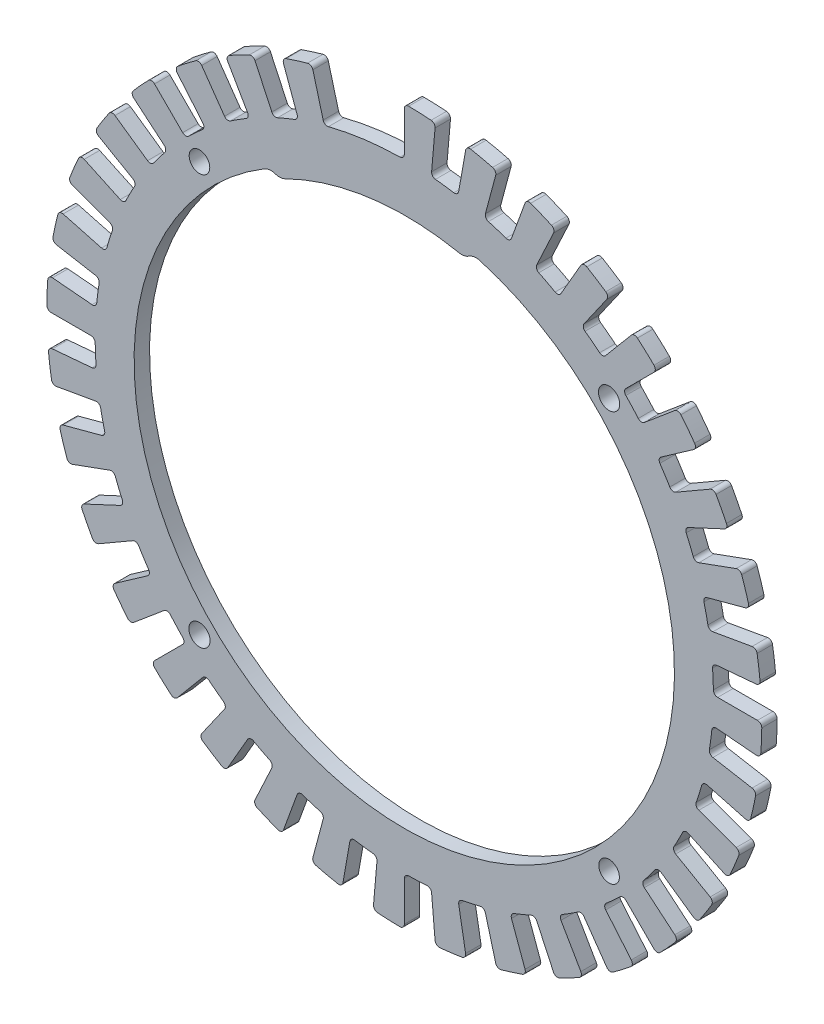
SolidWorks part; units mm, degrees
ref_plane "Front Plane" through (0, 0, 0) normal (0, 0, 1) x (1, 0, 0)
ref_plane "Top Plane" through (0, 0, 0) normal (0, 1, 0) x (1, 0, 0)
ref_plane "Right Plane" through (0, 0, 0) normal (1, 0, 0) x (0, 0, -1)
sketch "Sketch1" plane through (0, 0, 0) normal (0, 0, 1) x (1, 0, 0)
  line L0 (0, 82.7) -> (0, 71.5) construction
  line L1 (7.2078, 82.3853) -> (6.2316, 71.2279) construction
  line L2 (0, 71.5) -> (0, 0) construction
  line L3 (6.2316, 71.2279) -> (0, 0) construction
  line L4 (12.5883, 71.3918) -> (14.186, 80.4528) construction
  line L5 (12.5883, 71.3918) -> (0, 0) construction
  line L8 (0, 0) -> (47.3762, 47.3762) construction
  line L12 (50.5581, 50.5581) -> (47.3762, 47.3762) construction
  line L15 (47.3762, 47.3762) -> (44.1942, 44.1942) construction
  line L18 (7.3144, 72.1301) -> (6.3182, 72.2172) construction
  line L21 (7.3144, 72.1301) -> (7.2135, 71.1352) construction
  line L24 (12.5883, 71.3918) -> (11.6035, 71.5654) construction
  line L27 (11.6035, 71.5654) -> (11.4434, 70.5783) construction
  line L30 (1.0122, 82.6938) -> (1, 81.6939) construction
  line L33 (1, 81.6939) -> (0, 81.6939) construction
  line L36 (7.1201, 81.383) -> (6.1239, 81.4702) construction
  line L39 (6.1239, 81.4702) -> (6.1989, 82.4674) construction
  line L42 (7.1201, 81.383) -> (6.3182, 72.2172)
  line L45 (0, 81.6939) -> (0, 72.4931)
  line L48 (0, 72.4931) -> (-1, 72.4931) construction
  line L51 (-1, 72.4931) -> (-0.9862, 71.4932) construction
  line L109 (0, -82.7) -> (0, -71.5) [skipped]
  line L111 (14.3607, 81.4436) -> (12.4158, 70.4138) [skipped]
  line L115 (41.35, 71.6203) -> (35.75, 61.9208) [skipped]
  line L117 (53.1585, 63.3519) -> (45.9593, 54.7722) [skipped]
  line L118 (-63.3519, -53.1585) -> (-54.7722, -45.9593) [skipped]
  line L119 (63.3519, 53.1585) -> (54.7722, 45.9593) [skipped]
  line L121 (71.6203, 41.35) -> (61.9208, 35.75) [skipped]
  line L123 (77.7126, 28.2851) -> (67.188, 24.4544) [skipped]
  line L125 (81.4436, 14.3607) -> (70.4138, 12.4158) [skipped]
  line L127 (82.7, 0) -> (71.5, 0) [skipped]
  line L129 (81.4436, -14.3607) -> (70.4138, -12.4158) [skipped]
  line L131 (77.7126, -28.2851) -> (67.188, -24.4544) [skipped]
  line L133 (71.6203, -41.35) -> (61.9208, -35.75) [skipped]
  line L135 (63.3519, -53.1585) -> (54.7722, -45.9593) [skipped]
  line L137 (53.1585, -63.3519) -> (45.9593, -54.7722) [skipped]
  line L139 (41.35, -71.6203) -> (35.75, -61.9208) [skipped]
  line L141 (28.2851, -77.7126) -> (24.4544, -67.188) [skipped]
  line L142 (14.3607, -81.4436) -> (12.4158, -70.4138) [skipped]
  line L143 (34.9505, 74.9517) -> (30.2172, 64.801) [skipped]
  line L144 (47.4348, 67.7439) -> (41.0107, 58.5694) [skipped]
  line L145 (58.4777, 58.4777) -> (50.5581, 50.5581) [skipped]
  line L146 (67.7439, 47.4348) -> (58.5694, 41.0107) [skipped]
  line L147 (74.9517, 34.9505) -> (64.801, 30.2172) [skipped]
  line L148 (79.8821, 21.4043) -> (69.0637, 18.5056) [skipped]
  line L149 (82.3853, 7.2078) -> (71.2279, 6.2316) [skipped]
  line L150 (82.3853, -7.2078) -> (71.2279, -6.2316) [skipped]
  line L151 (79.8821, -21.4043) -> (69.0637, -18.5056) [skipped]
  line L152 (74.9517, -34.9505) -> (64.801, -30.2172) [skipped]
  line L153 (67.7439, -47.4348) -> (58.5694, -41.0107) [skipped]
  line L154 (58.4777, -58.4777) -> (50.5581, -50.5581) [skipped]
  line L155 (47.4348, -67.7439) -> (41.0107, -58.5694) [skipped]
  line L156 (34.9505, -74.9517) -> (30.2172, -64.801) [skipped]
  line L157 (21.4043, -79.8821) -> (18.5056, -69.0637) [skipped]
  line L158 (7.2078, -82.3853) -> (6.2316, -71.2279) [skipped]
  line L159 (-7.2078, -82.3853) -> (-6.2316, -71.2279) [skipped]
  line L160 (-21.4043, -79.8821) -> (-18.5056, -69.0637) [skipped]
  line L161 (-34.9505, -74.9517) -> (-30.2172, -64.801) [skipped]
  line L162 (-47.4348, -67.7439) -> (-41.0107, -58.5694) [skipped]
  line L163 (-58.4777, -58.4777) -> (-50.5581, -50.5581) [skipped]
  line L164 (-67.7439, -47.4348) -> (-58.5694, -41.0107) [skipped]
  line L165 (-74.9517, -34.9505) -> (-64.801, -30.2172) [skipped]
  line L166 (-79.8821, -21.4043) -> (-69.0637, -18.5056) [skipped]
  line L167 (-82.3853, -7.2078) -> (-71.2279, -6.2316) [skipped]
  line L168 (-82.3853, 7.2078) -> (-71.2279, 6.2316) [skipped]
  line L169 (-79.8821, 21.4043) -> (-69.0637, 18.5056) [skipped]
  line L170 (-74.9517, 34.9505) -> (-64.801, 30.2172) [skipped]
  line L171 (-67.7439, 47.4348) -> (-58.5694, 41.0107) [skipped]
  line L172 (-58.4777, 58.4777) -> (-50.5581, 50.5581) [skipped]
  line L173 (-47.4348, 67.7439) -> (-41.0107, 58.5694) [skipped]
  line L174 (-34.9505, 74.9517) -> (-30.2172, 64.801) [skipped]
  line L175 (-21.4043, 79.8821) -> (-18.5056, 69.0637) [skipped]
  line L176 (21.4043, 79.8821) -> (18.5056, 69.0637) [skipped]
  line L209 (0, 0) -> (-47.3762, -47.3762) construction
  line L210 (0, 0) -> (-47.3762, 47.3762) construction
  line L211 (0, 0) -> (47.3762, -47.3762) construction
  line L212 (14.186, 80.4528) -> (12.5883, 71.3918)
  line L213 (21.1439, 78.9102) -> (18.7626, 70.023)
  line L214 (27.941, 76.7671) -> (24.7941, 68.1212)
  line L215 (34.5253, 74.0398) -> (30.6369, 65.7011)
  line L216 (40.8469, 70.749) -> (36.2466, 62.7809)
  line L217 (46.8577, 66.9197) -> (41.5803, 59.3829)
  line L218 (52.5118, 62.5811) -> (46.5977, 55.5329)
  line L219 (57.7663, 57.7663) -> (51.2604, 51.2604)
  line L220 (62.5811, 52.5118) -> (55.5329, 46.5977)
  line L221 (66.9197, 46.8577) -> (59.3829, 41.5803)
  line L222 (70.749, 40.8469) -> (62.7809, 36.2466)
  line L223 (74.0398, 34.5253) -> (65.7011, 30.6369)
  line L224 (76.7671, 27.941) -> (68.1212, 24.7941)
  line L225 (78.9102, 21.1439) -> (70.023, 18.7626)
  line L226 (80.4528, 14.186) -> (71.3918, 12.5883)
  line L227 (81.383, 7.1201) -> (72.2172, 6.3182)
  line L228 (81.6939, 0) -> (72.4931, 0)
  line L229 (81.383, -7.1201) -> (72.2172, -6.3182)
  line L230 (80.4528, -14.186) -> (71.3918, -12.5883)
  line L231 (78.9102, -21.1439) -> (70.023, -18.7626)
  line L232 (76.7671, -27.941) -> (68.1212, -24.7941)
  line L233 (74.0398, -34.5253) -> (65.7011, -30.6369)
  line L234 (70.749, -40.8469) -> (62.7809, -36.2466)
  line L235 (66.9197, -46.8577) -> (59.3829, -41.5803)
  line L236 (62.5811, -52.5118) -> (55.5329, -46.5977)
  line L237 (57.7663, -57.7663) -> (51.2604, -51.2604)
  line L238 (52.5118, -62.5811) -> (46.5977, -55.5329)
  line L239 (46.8577, -66.9197) -> (41.5803, -59.3829)
  line L240 (40.8469, -70.749) -> (36.2466, -62.7809)
  line L241 (34.5253, -74.0398) -> (30.6369, -65.7011)
  line L242 (27.941, -76.7671) -> (24.7941, -68.1212)
  line L243 (21.1439, -78.9102) -> (18.7626, -70.023)
  line L244 (14.186, -80.4528) -> (12.5883, -71.3918)
  line L245 (7.1201, -81.383) -> (6.3182, -72.2172)
  line L246 (0, -81.6939) -> (0, -72.4931)
  line L247 (-7.1201, -81.383) -> (-6.3182, -72.2172)
  line L248 (-14.186, -80.4528) -> (-12.5883, -71.3918)
  line L249 (-21.1439, -78.9102) -> (-18.7626, -70.023)
  line L250 (-27.941, -76.7671) -> (-24.7941, -68.1212)
  line L251 (-34.5253, -74.0398) -> (-30.6369, -65.7011)
  line L252 (-40.8469, -70.749) -> (-36.2466, -62.7809)
  line L253 (-46.8577, -66.9197) -> (-41.5803, -59.3829)
  line L254 (-52.5118, -62.5811) -> (-46.5977, -55.5329)
  line L255 (-57.7663, -57.7663) -> (-51.2604, -51.2604)
  line L256 (-62.5811, -52.5118) -> (-55.5329, -46.5977)
  line L257 (-66.9197, -46.8577) -> (-59.3829, -41.5803)
  line L258 (-70.749, -40.8469) -> (-62.7809, -36.2466)
  line L259 (-74.0398, -34.5253) -> (-65.7011, -30.6369)
  line L260 (-76.7671, -27.941) -> (-68.1212, -24.7941)
  line L261 (-78.9102, -21.1439) -> (-70.023, -18.7626)
  line L262 (-80.4528, -14.186) -> (-71.3918, -12.5883)
  line L263 (-81.383, -7.1201) -> (-72.2172, -6.3182)
  line L264 (-81.6939, 0) -> (-72.4931, 0)
  line L265 (-81.383, 7.1201) -> (-72.2172, 6.3182)
  line L266 (-80.4528, 14.186) -> (-71.3918, 12.5883)
  line L267 (-78.9102, 21.1439) -> (-70.023, 18.7626)
  line L268 (-76.7671, 27.941) -> (-68.1212, 24.7941)
  line L269 (-74.0398, 34.5253) -> (-65.7011, 30.6369)
  line L270 (-70.749, 40.8469) -> (-62.7809, 36.2466)
  line L271 (-66.9197, 46.8577) -> (-59.3829, 41.5803)
  line L272 (-62.5811, 52.5118) -> (-55.5329, 46.5977)
  line L273 (-57.7663, 57.7663) -> (-51.2604, 51.2604)
  line L274 (-52.5118, 62.5811) -> (-46.5977, 55.5329)
  line L275 (-46.8577, 66.9197) -> (-41.5803, 59.3829)
  line L276 (-40.8469, 70.749) -> (-36.2466, 62.7809)
  line L277 (-34.5253, 74.0398) -> (-30.6369, 65.7011)
  line L278 (-27.941, 76.7671) -> (-24.7941, 68.1212)
  line L279 (-21.1439, 78.9102) -> (-18.7626, 70.023)
  line L280 (-0.9864, 71.4932) -> (-0.9862, 71.4932)
  line L281 (-32.3995, 53.4464) -> (-30.8444, 50.881) construction
  line L282 (-30.8444, 50.881) -> (-29.8635, 53.7161) construction
  line L283 (-29.8635, 53.7161) -> (-28.8826, 56.5512) construction
  line L284 (-28.8826, 56.5512) -> (-27.5181, 53.8795) construction
  line L285 (17.4626, 60.0109) -> (16.6244, 57.1304) construction
  line L286 (16.6244, 57.1304) -> (14.9432, 59.615) construction
  line L289 (13.262, 62.0997) -> (14.9432, 59.615) construction
  line L290 (-7.4414, 56.5227) -> (0, 0) construction
  line L291 (-27.5181, 53.8795) -> (-7.4414, 56.5227) construction
  line L292 (-7.4414, 56.5227) -> (12.6354, 59.1658) construction
  line L293 (13.262, 62.0997) -> (12.6354, 59.1658) construction
  line L294 (-28.4278, 55.6607) -> (13.0531, 61.1217) construction
  circle A0 centre (0, 0) radius 82.7 construction
  arc A1 (-32.3995, 53.4464) -> (17.4626, 60.0109) centre (0, 0) ccw
  circle A73 centre (47.3762, 47.3762) radius 2.4585
  circle A74 centre (47.3762, 47.3762) radius 2.987 construction
  arc A78 (0, 71.5) -> (6.2316, 71.2279) centre (0, 0) cw construction
  arc A79 (6.3182, 72.2172) -> (7.2135, 71.1352) centre (7.3144, 72.1301) ccw
  arc A80 (11.4434, 70.5783) -> (12.5883, 71.3918) centre (11.6035, 71.5654) ccw construction
  arc A81 (7.1201, 81.383) -> (6.1989, 82.4674) centre (6.1239, 81.4702) ccw
  arc A82 (0, 81.6939) -> (1.0122, 82.6938) centre (1, 81.6939) cw
  arc A83 (6.5367, 74.7146) -> (13.0236, 73.8606) centre (0, 0) cw [skipped]
  arc A84 (7.2135, 71.1352) -> (11.4434, 70.5783) centre (0, 0) cw
  arc A85 (0, 82.7) -> (7.2078, 82.3853) centre (0, 0) cw [skipped]
  arc A86 (1.0122, 82.6938) -> (6.1989, 82.4674) centre (0, 0) cw
  arc A87 (28.2851, 77.7126) -> (34.9505, 74.9517) centre (0, 0) cw [skipped]
  arc A88 (31.6964, 67.9731) -> (37.5, 64.9519) centre (0, 0) cw [skipped]
  arc A89 (41.35, 71.6203) -> (47.4348, 67.7439) centre (0, 0) cw [skipped]
  arc A90 (43.0182, 61.4364) -> (48.2091, 57.4533) centre (0, 0) cw [skipped]
  arc A91 (53.1585, 63.3519) -> (58.4777, 58.4777) centre (0, 0) cw [skipped]
  arc A92 (53.033, 53.033) -> (57.4533, 48.2091) centre (0, 0) cw [skipped]
  arc A93 (63.3519, 53.1585) -> (67.7439, 47.4348) centre (0, 0) cw [skipped]
  arc A94 (61.4364, 43.0182) -> (64.9519, 37.5) centre (0, 0) cw [skipped]
  arc A95 (71.6203, 41.35) -> (74.9517, 34.9505) centre (0, 0) cw [skipped]
  arc A96 (67.9731, 31.6964) -> (70.4769, 25.6515) centre (0, 0) cw [skipped]
  arc A97 (77.7126, 28.2851) -> (79.8821, 21.4043) centre (0, 0) cw [skipped]
  arc A98 (72.4444, 19.4114) -> (73.8606, 13.0236) centre (0, 0) cw [skipped]
  arc A99 (81.4436, 14.3607) -> (82.3853, 7.2078) centre (0, 0) cw [skipped]
  arc A100 (74.7146, 6.5367) -> (75, 0) centre (0, 0) cw [skipped]
  arc A101 (82.7, 0) -> (82.3853, -7.2078) centre (0, 0) cw [skipped]
  arc A102 (74.7146, -6.5367) -> (73.8606, -13.0236) centre (0, 0) cw [skipped]
  arc A103 (81.4436, -14.3607) -> (79.8821, -21.4043) centre (0, 0) cw [skipped]
  arc A104 (72.4444, -19.4114) -> (70.4769, -25.6515) centre (0, 0) cw [skipped]
  arc A105 (77.7126, -28.2851) -> (74.9517, -34.9505) centre (0, 0) cw [skipped]
  arc A106 (67.9731, -31.6964) -> (64.9519, -37.5) centre (0, 0) cw [skipped]
  arc A107 (71.6203, -41.35) -> (67.7439, -47.4348) centre (0, 0) cw [skipped]
  arc A108 (61.4364, -43.0182) -> (57.4533, -48.2091) centre (0, 0) cw [skipped]
  arc A109 (63.3519, -53.1585) -> (58.4777, -58.4777) centre (0, 0) cw [skipped]
  arc A110 (53.033, -53.033) -> (48.2091, -57.4533) centre (0, 0) cw [skipped]
  arc A111 (53.1585, -63.3519) -> (47.4348, -67.7439) centre (0, 0) cw [skipped]
  arc A112 (43.0182, -61.4364) -> (37.5, -64.9519) centre (0, 0) cw [skipped]
  arc A113 (41.35, -71.6203) -> (34.9505, -74.9517) centre (0, 0) cw [skipped]
  arc A114 (31.6964, -67.9731) -> (25.6515, -70.4769) centre (0, 0) cw [skipped]
  arc A115 (28.2851, -77.7126) -> (21.4043, -79.8821) centre (0, 0) cw [skipped]
  arc A116 (19.4114, -72.4444) -> (13.0236, -73.8606) centre (0, 0) cw [skipped]
  arc A117 (14.3607, -81.4436) -> (7.2078, -82.3853) centre (0, 0) cw [skipped]
  arc A118 (6.5367, -74.7146) -> (0, -75) centre (0, 0) cw [skipped]
  arc A119 (0, -82.7) -> (-7.2078, -82.3853) centre (0, 0) cw [skipped]
  arc A120 (-6.5367, -74.7146) -> (-13.0236, -73.8606) centre (0, 0) cw [skipped]
  arc A121 (-14.3607, -81.4436) -> (-21.4043, -79.8821) centre (0, 0) cw [skipped]
  arc A122 (-28.2851, -77.7126) -> (-34.9505, -74.9517) centre (0, 0) cw [skipped]
  arc A123 (-19.4114, -72.4444) -> (-25.6515, -70.4769) centre (0, 0) cw [skipped]
  arc A124 (-31.6964, -67.9731) -> (-37.5, -64.9519) centre (0, 0) cw [skipped]
  arc A125 (-41.35, -71.6203) -> (-47.4348, -67.7439) centre (0, 0) cw [skipped]
  arc A126 (-43.0182, -61.4364) -> (-48.2091, -57.4533) centre (0, 0) cw [skipped]
  arc A127 (-53.1585, -63.3519) -> (-58.4777, -58.4777) centre (0, 0) cw [skipped]
  arc A128 (-53.033, -53.033) -> (-57.4533, -48.2091) centre (0, 0) cw [skipped]
  arc A129 (-63.3519, -53.1585) -> (-67.7439, -47.4348) centre (0, 0) cw [skipped]
  arc A130 (-61.4364, -43.0182) -> (-64.9519, -37.5) centre (0, 0) cw [skipped]
  arc A131 (-71.6203, -41.35) -> (-74.9517, -34.9505) centre (0, 0) cw [skipped]
  arc A132 (-67.9731, -31.6964) -> (-70.4769, -25.6515) centre (0, 0) cw [skipped]
  arc A133 (-77.7126, -28.2851) -> (-79.8821, -21.4043) centre (0, 0) cw [skipped]
  arc A134 (-72.4444, -19.4114) -> (-73.8606, -13.0236) centre (0, 0) cw [skipped]
  arc A135 (-81.4436, -14.3607) -> (-82.3853, -7.2078) centre (0, 0) cw [skipped]
  arc A136 (-74.7146, -6.5367) -> (-75, 0) centre (0, 0) cw [skipped]
  arc A137 (-82.7, 0) -> (-82.3853, 7.2078) centre (0, 0) cw [skipped]
  arc A138 (-74.7146, 6.5367) -> (-73.8606, 13.0236) centre (0, 0) cw [skipped]
  arc A139 (-81.4436, 14.3607) -> (-79.8821, 21.4043) centre (0, 0) cw [skipped]
  arc A140 (-72.4444, 19.4114) -> (-70.4769, 25.6515) centre (0, 0) cw [skipped]
  arc A141 (-77.7126, 28.2851) -> (-74.9517, 34.9505) centre (0, 0) cw [skipped]
  arc A142 (-67.9731, 31.6964) -> (-64.9519, 37.5) centre (0, 0) cw [skipped]
  arc A143 (-71.6203, 41.35) -> (-67.7439, 47.4348) centre (0, 0) cw [skipped]
  arc A144 (-61.4364, 43.0182) -> (-57.4533, 48.2091) centre (0, 0) cw [skipped]
  arc A145 (-63.3519, 53.1585) -> (-58.4777, 58.4777) centre (0, 0) cw [skipped]
  arc A146 (-53.033, 53.033) -> (-48.2091, 57.4533) centre (0, 0) cw [skipped]
  arc A147 (-53.1585, 63.3519) -> (-47.4348, 67.7439) centre (0, 0) cw [skipped]
  arc A148 (-43.0182, 61.4364) -> (-37.5, 64.9519) centre (0, 0) cw [skipped]
  arc A149 (-41.35, 71.6203) -> (-34.9505, 74.9517) centre (0, 0) cw [skipped]
  arc A150 (-31.6964, 67.9731) -> (-25.6515, 70.4769) centre (0, 0) cw [skipped]
  arc A151 (-28.2851, 77.7126) -> (-21.4043, 79.8821) centre (0, 0) cw [skipped]
  arc A152 (-19.4114, 72.4444) -> (-13.0236, 73.8606) centre (0, 0) cw [skipped]
  arc A153 (14.3607, 81.4436) -> (21.4043, 79.8821) centre (0, 0) cw [skipped]
  arc A154 (19.4114, 72.4444) -> (25.6515, 70.4769) centre (0, 0) cw [skipped]
  arc A155 (0, 72.4931) -> (-0.9862, 71.4932) centre (-1, 72.4931) cw
  circle A367 centre (-47.3762, -47.3762) radius 2.4585
  circle A368 centre (47.3762, -47.3762) radius 2.3813
  circle A369 centre (-47.3762, 47.3762) radius 2.3812
  circle A370 centre (0, 0) radius 71.5 construction
  arc A371 (12.5883, 71.3918) -> (11.4434, 70.5783) centre (11.6035, 71.5654) cw
  arc A372 (14.186, 80.4528) -> (15.3565, 81.2617) centre (15.1708, 80.2791) cw
  arc A373 (15.3565, 81.2617) -> (20.425, 80.1381) centre (0, 0) cw
  arc A374 (21.1439, 78.9102) -> (20.425, 80.1381) centre (20.178, 79.169) ccw
  arc A375 (18.7626, 70.023) -> (19.4564, 68.8019) centre (19.7285, 69.7641) ccw
  arc A376 (19.4564, 68.8019) -> (23.5254, 67.5189) centre (0, 0) cw
  arc A377 (24.7941, 68.1212) -> (23.5254, 67.5189) centre (23.8544, 68.4633) cw
  arc A378 (27.941, 76.7671) -> (29.2341, 77.3606) centre (28.8806, 76.4251) cw
  arc A379 (29.2341, 77.3606) -> (34.0305, 75.3738) centre (0, 0) cw
  arc A380 (34.5253, 74.0398) -> (34.0305, 75.3738) centre (33.619, 74.4624) ccw
  arc A381 (30.6369, 65.7011) -> (31.1081, 64.3781) centre (31.5432, 65.2784) ccw
  arc A382 (31.1081, 64.3781) -> (34.8925, 62.408) centre (0, 0) cw
  arc A384 (36.2466, 62.7809) -> (34.8925, 62.408) centre (35.3805, 63.2809) cw
  arc A385 (40.8469, 70.749) -> (42.2235, 71.1088) centre (41.713, 70.249) cw
  arc A386 (42.2235, 71.1088) -> (46.602, 68.3194) centre (0, 0) cw
  arc A387 (46.8577, 66.9197) -> (46.602, 68.3194) centre (46.0385, 67.4933) ccw
  arc A388 (41.5803, 59.3829) -> (41.8147, 57.9981) centre (42.3995, 58.8093) ccw
  arc A389 (41.8147, 57.9981) -> (45.1995, 55.4009) centre (0, 0) cw
  arc A390 (46.5977, 55.5329) -> (45.1995, 55.4009) centre (45.8316, 56.1757) cw
  arc A391 (52.5118, 62.5811) -> (53.93, 62.6965) centre (53.2779, 61.9384) cw
  arc A392 (53.93, 62.6965) -> (57.7576, 59.1891) centre (0, 0) cw
  arc A393 (57.7663, 57.7663) -> (57.7576, 59.1891) centre (57.0592, 58.4734) ccw
  arc A394 (51.2604, 51.2604) -> (51.2507, 49.856) centre (51.9675, 50.5533) ccw
  arc A395 (51.2507, 49.856) -> (54.133, 46.7104) centre (0, 0) cw
  arc A396 (55.5329, 46.5977) -> (54.133, 46.7104) centre (54.8902, 47.3637) cw
  arc A397 (62.5811, 52.5118) -> (63.9978, 52.3791) centre (63.2239, 51.7458) cw
  arc A398 (63.9978, 52.3791) -> (67.1582, 48.2604) centre (0, 0) cw
  arc A399 (66.9197, 46.8577) -> (67.1582, 48.2604) centre (66.3461, 47.6768) ccw
  arc A400 (59.3829, 41.5803) -> (59.1295, 40.199) centre (59.9565, 40.7612) ccw
  arc A401 (59.1295, 40.199) -> (61.4218, 36.6007) centre (0, 0) cw
  arc A402 (62.7809, 36.2466) -> (61.4218, 36.6007) centre (62.2809, 37.1126) cw
  arc A403 (70.749, 40.8469) -> (72.1211, 40.4703) centre (71.249, 39.9809) cw
  arc A404 (72.1211, 40.4703) -> (74.5182, 35.8653) centre (0, 0) cw
  arc A405 (74.0398, 34.5253) -> (74.5182, 35.8653) centre (73.6172, 35.4316) ccw
  arc A406 (65.7011, 30.6369) -> (65.2116, 29.3205) centre (66.1237, 29.7306) ccw
  arc A407 (65.2116, 29.3205) -> (66.8443, 25.3788) centre (0, 0) cw
  arc A408 (68.1212, 24.7941) -> (66.8443, 25.3788) centre (67.7792, 25.7338) cw
  arc A409 (76.7671, 27.941) -> (78.053, 27.3318) centre (77.1092, 27.0013) cw
  arc A410 (78.053, 27.3318) -> (79.6141, 22.3805) centre (0, 0) cw
  arc A411 (78.9102, 21.1439) -> (79.6141, 22.3805) centre (78.6514, 22.1099) ccw
  arc A412 (70.023, 18.7626) -> (69.3124, 17.5512) centre (70.2818, 17.7967) ccw
  arc A413 (69.3124, 17.5512) -> (70.2358, 13.3859) centre (0, 0) cw
  arc A414 (71.3918, 12.5883) -> (70.2358, 13.3859) centre (71.2181, 13.5731) cw
  arc A415 (80.4528, 14.186) -> (81.6133, 13.3628) centre (80.6264, 13.2012) cw
  arc A416 (81.6133, 13.3628) -> (82.2909, 8.2156) centre (0, 0) cw
  arc A417 (81.383, 7.1201) -> (82.2909, 8.2156) centre (81.2959, 8.1163) ccw
  arc A418 (72.2172, 6.3182) -> (71.3071, 5.2486) centre (72.3044, 5.322) ccw
  arc A419 (71.3071, 5.2486) -> (71.4932, 0.9862) centre (0, 0) cw
  arc A420 (72.4931, 0) -> (71.4932, 0.9862) centre (72.4931, 1) cw
  arc A421 (81.6939, 0) -> (82.6938, -1.0122) centre (81.6939, -1) cw
  arc A422 (82.6938, -1.0122) -> (82.4674, -6.1989) centre (0, 0) cw
  arc A423 (81.383, -7.1201) -> (82.4674, -6.1989) centre (81.4702, -6.1239) ccw
  arc A424 (72.2172, -6.3182) -> (71.1352, -7.2135) centre (72.1301, -7.3144) ccw
  arc A425 (71.1352, -7.2135) -> (70.5783, -11.4434) centre (0, 0) cw
  arc A426 (71.3918, -12.5883) -> (70.5783, -11.4434) centre (71.5654, -11.6035) cw
  arc A427 (80.4528, -14.186) -> (81.2617, -15.3565) centre (80.2791, -15.1708) cw
  arc A428 (81.2617, -15.3565) -> (80.1381, -20.425) centre (0, 0) cw
  arc A429 (78.9102, -21.1439) -> (80.1381, -20.425) centre (79.169, -20.178) ccw
  arc A430 (70.023, -18.7626) -> (68.8019, -19.4564) centre (69.7641, -19.7285) ccw
  arc A431 (68.8019, -19.4564) -> (67.5189, -23.5254) centre (0, 0) cw
  arc A432 (68.1212, -24.7941) -> (67.5189, -23.5254) centre (68.4633, -23.8544) cw
  arc A433 (76.7671, -27.941) -> (77.3606, -29.2341) centre (76.4251, -28.8806) cw
  arc A434 (77.3606, -29.2341) -> (75.3738, -34.0305) centre (0, 0) cw
  arc A435 (74.0398, -34.5253) -> (75.3738, -34.0305) centre (74.4624, -33.619) ccw
  arc A436 (65.7011, -30.6369) -> (64.3781, -31.1081) centre (65.2784, -31.5432) ccw
  arc A437 (64.3781, -31.1081) -> (62.408, -34.8925) centre (0, 0) cw
  arc A438 (62.7809, -36.2466) -> (62.408, -34.8925) centre (63.2809, -35.3805) cw
  arc A439 (70.749, -40.8469) -> (71.1088, -42.2235) centre (70.249, -41.713) cw
  arc A440 (71.1088, -42.2235) -> (68.3194, -46.602) centre (0, 0) cw
  arc A441 (66.9197, -46.8577) -> (68.3194, -46.602) centre (67.4933, -46.0385) ccw
  arc A442 (59.3829, -41.5803) -> (57.9981, -41.8147) centre (58.8093, -42.3995) ccw
  arc A443 (57.9981, -41.8147) -> (55.4009, -45.1995) centre (0, 0) cw
  arc A444 (55.5329, -46.5977) -> (55.4009, -45.1995) centre (56.1757, -45.8316) cw
  arc A445 (62.5811, -52.5118) -> (62.6965, -53.93) centre (61.9384, -53.2779) cw
  arc A446 (62.6965, -53.93) -> (59.1891, -57.7576) centre (0, 0) cw
  arc A447 (57.7663, -57.7663) -> (59.1891, -57.7576) centre (58.4734, -57.0592) ccw
  arc A448 (51.2604, -51.2604) -> (49.856, -51.2507) centre (50.5533, -51.9675) ccw
  arc A449 (49.856, -51.2507) -> (46.7104, -54.133) centre (0, 0) cw
  arc A450 (46.5977, -55.5329) -> (46.7104, -54.133) centre (47.3637, -54.8902) cw
  arc A451 (52.5118, -62.5811) -> (52.3791, -63.9978) centre (51.7458, -63.2239) cw
  arc A452 (52.3791, -63.9978) -> (48.2604, -67.1582) centre (0, 0) cw
  arc A453 (46.8577, -66.9197) -> (48.2604, -67.1582) centre (47.6768, -66.3461) ccw
  arc A454 (41.5803, -59.3829) -> (40.199, -59.1295) centre (40.7612, -59.9565) ccw
  arc A455 (40.199, -59.1295) -> (36.6007, -61.4218) centre (0, 0) cw
  arc A456 (36.2466, -62.7809) -> (36.6007, -61.4218) centre (37.1126, -62.2809) cw
  arc A457 (40.8469, -70.749) -> (40.4703, -72.1211) centre (39.9809, -71.249) cw
  arc A458 (40.4703, -72.1211) -> (35.8653, -74.5182) centre (0, 0) cw
  arc A459 (34.5253, -74.0398) -> (35.8653, -74.5182) centre (35.4316, -73.6172) ccw
  arc A460 (30.6369, -65.7011) -> (29.3205, -65.2116) centre (29.7306, -66.1237) ccw
  arc A461 (29.3205, -65.2116) -> (25.3788, -66.8443) centre (0, 0) cw
  arc A462 (24.7941, -68.1212) -> (25.3788, -66.8443) centre (25.7338, -67.7792) cw
  arc A463 (27.941, -76.7671) -> (27.3318, -78.053) centre (27.0013, -77.1092) cw
  arc A464 (27.3318, -78.053) -> (22.3805, -79.6141) centre (0, 0) cw
  arc A465 (21.1439, -78.9102) -> (22.3805, -79.6141) centre (22.1099, -78.6514) ccw
  arc A466 (18.7626, -70.023) -> (17.5512, -69.3124) centre (17.7967, -70.2818) ccw
  arc A467 (17.5512, -69.3124) -> (13.3859, -70.2358) centre (0, 0) cw
  arc A468 (12.5883, -71.3918) -> (13.3859, -70.2358) centre (13.5731, -71.2181) cw
  arc A469 (14.186, -80.4528) -> (13.3628, -81.6133) centre (13.2012, -80.6264) cw
  arc A470 (13.3628, -81.6133) -> (8.2156, -82.2909) centre (0, 0) cw
  arc A471 (7.1201, -81.383) -> (8.2156, -82.2909) centre (8.1163, -81.2959) ccw
  arc A472 (6.3182, -72.2172) -> (5.2486, -71.3071) centre (5.322, -72.3044) ccw
  arc A473 (5.2486, -71.3071) -> (0.9862, -71.4932) centre (0, 0) cw
  arc A474 (0, -72.4931) -> (0.9862, -71.4932) centre (1, -72.4931) cw
  arc A475 (0, -81.6939) -> (-1.0122, -82.6938) centre (-1, -81.6939) cw
  arc A476 (-1.0122, -82.6938) -> (-6.1989, -82.4674) centre (0, 0) cw
  arc A477 (-7.1201, -81.383) -> (-6.1989, -82.4674) centre (-6.1239, -81.4702) ccw
  arc A478 (-6.3182, -72.2172) -> (-7.2135, -71.1352) centre (-7.3144, -72.1301) ccw
  arc A479 (-7.2135, -71.1352) -> (-11.4434, -70.5783) centre (0, 0) cw
  arc A480 (-12.5883, -71.3918) -> (-11.4434, -70.5783) centre (-11.6035, -71.5654) cw
  arc A481 (-14.186, -80.4528) -> (-15.3565, -81.2617) centre (-15.1708, -80.2791) cw
  arc A482 (-15.3565, -81.2617) -> (-20.425, -80.1381) centre (0, 0) cw
  arc A483 (-21.1439, -78.9102) -> (-20.425, -80.1381) centre (-20.178, -79.169) ccw
  arc A484 (-18.7626, -70.023) -> (-19.4564, -68.8019) centre (-19.7285, -69.7641) ccw
  arc A485 (-19.4564, -68.8019) -> (-23.5254, -67.5189) centre (0, 0) cw
  arc A486 (-24.7941, -68.1212) -> (-23.5254, -67.5189) centre (-23.8544, -68.4633) cw
  arc A487 (-27.941, -76.7671) -> (-29.2341, -77.3606) centre (-28.8806, -76.4251) cw
  arc A488 (-29.2341, -77.3606) -> (-34.0305, -75.3738) centre (0, 0) cw
  arc A489 (-34.5253, -74.0398) -> (-34.0305, -75.3738) centre (-33.619, -74.4624) ccw
  arc A490 (-30.6369, -65.7011) -> (-31.1081, -64.3781) centre (-31.5432, -65.2784) ccw
  arc A491 (-31.1081, -64.3781) -> (-34.8925, -62.408) centre (0, 0) cw
  arc A492 (-36.2466, -62.7809) -> (-34.8925, -62.408) centre (-35.3805, -63.2809) cw
  arc A493 (-40.8469, -70.749) -> (-42.2235, -71.1088) centre (-41.713, -70.249) cw
  arc A494 (-42.2235, -71.1088) -> (-46.602, -68.3194) centre (0, 0) cw
  arc A495 (-46.8577, -66.9197) -> (-46.602, -68.3194) centre (-46.0385, -67.4933) ccw
  arc A496 (-41.5803, -59.3829) -> (-41.8147, -57.9981) centre (-42.3995, -58.8093) ccw
  arc A497 (-41.8147, -57.9981) -> (-45.1995, -55.4009) centre (0, 0) cw
  arc A498 (-46.5977, -55.5329) -> (-45.1995, -55.4009) centre (-45.8316, -56.1757) cw
  arc A499 (-52.5118, -62.5811) -> (-53.93, -62.6965) centre (-53.2779, -61.9384) cw
  arc A500 (-53.93, -62.6965) -> (-57.7576, -59.1891) centre (0, 0) cw
  arc A501 (-57.7663, -57.7663) -> (-57.7576, -59.1891) centre (-57.0592, -58.4734) ccw
  arc A502 (-51.2604, -51.2604) -> (-51.2507, -49.856) centre (-51.9675, -50.5533) ccw
  arc A503 (-51.2507, -49.856) -> (-54.133, -46.7104) centre (0, 0) cw
  arc A504 (-55.5329, -46.5977) -> (-54.133, -46.7104) centre (-54.8902, -47.3637) cw
  arc A505 (-62.5811, -52.5118) -> (-63.9978, -52.3791) centre (-63.2239, -51.7458) cw
  arc A506 (-63.9978, -52.3791) -> (-67.1582, -48.2604) centre (0, 0) cw
  arc A507 (-66.9197, -46.8577) -> (-67.1582, -48.2604) centre (-66.3461, -47.6768) ccw
  arc A508 (-59.3829, -41.5803) -> (-59.1295, -40.199) centre (-59.9565, -40.7612) ccw
  arc A509 (-59.1295, -40.199) -> (-61.4218, -36.6007) centre (0, 0) cw
  arc A510 (-62.7809, -36.2466) -> (-61.4218, -36.6007) centre (-62.2809, -37.1126) cw
  arc A511 (-70.749, -40.8469) -> (-72.1211, -40.4703) centre (-71.249, -39.9809) cw
  arc A512 (-72.1211, -40.4703) -> (-74.5182, -35.8653) centre (0, 0) cw
  arc A513 (-74.0398, -34.5253) -> (-74.5182, -35.8653) centre (-73.6172, -35.4316) ccw
  arc A514 (-65.7011, -30.6369) -> (-65.2116, -29.3205) centre (-66.1237, -29.7306) ccw
  arc A515 (-65.2116, -29.3205) -> (-66.8443, -25.3788) centre (0, 0) cw
  arc A516 (-68.1212, -24.7941) -> (-66.8443, -25.3788) centre (-67.7792, -25.7338) cw
  arc A517 (-76.7671, -27.941) -> (-78.053, -27.3318) centre (-77.1092, -27.0013) cw
  arc A518 (-78.053, -27.3318) -> (-79.6141, -22.3805) centre (0, 0) cw
  arc A519 (-78.9102, -21.1439) -> (-79.6141, -22.3805) centre (-78.6514, -22.1099) ccw
  arc A520 (-70.023, -18.7626) -> (-69.3124, -17.5512) centre (-70.2818, -17.7967) ccw
  arc A521 (-69.3124, -17.5512) -> (-70.2358, -13.3859) centre (0, 0) cw
  arc A522 (-71.3918, -12.5883) -> (-70.2358, -13.3859) centre (-71.2181, -13.5731) cw
  arc A523 (-80.4528, -14.186) -> (-81.6133, -13.3628) centre (-80.6264, -13.2012) cw
  arc A524 (-81.6133, -13.3628) -> (-82.2909, -8.2156) centre (0, 0) cw
  arc A525 (-81.383, -7.1201) -> (-82.2909, -8.2156) centre (-81.2959, -8.1163) ccw
  arc A526 (-72.2172, -6.3182) -> (-71.3071, -5.2486) centre (-72.3044, -5.322) ccw
  arc A527 (-71.3071, -5.2486) -> (-71.4932, -0.9862) centre (0, 0) cw
  arc A528 (-72.4931, 0) -> (-71.4932, -0.9862) centre (-72.4931, -1) cw
  arc A529 (-81.6939, 0) -> (-82.6938, 1.0122) centre (-81.6939, 1) cw
  arc A530 (-82.6938, 1.0122) -> (-82.4674, 6.1989) centre (0, 0) cw
  arc A531 (-81.383, 7.1201) -> (-82.4674, 6.1989) centre (-81.4702, 6.1239) ccw
  arc A532 (-72.2172, 6.3182) -> (-71.1352, 7.2135) centre (-72.1301, 7.3144) ccw
  arc A533 (-71.1352, 7.2135) -> (-70.5783, 11.4434) centre (0, 0) cw
  arc A534 (-71.3918, 12.5883) -> (-70.5783, 11.4434) centre (-71.5654, 11.6035) cw
  arc A535 (-80.4528, 14.186) -> (-81.2617, 15.3565) centre (-80.2791, 15.1708) cw
  arc A536 (-81.2617, 15.3565) -> (-80.1381, 20.425) centre (0, 0) cw
  arc A537 (-78.9102, 21.1439) -> (-80.1381, 20.425) centre (-79.169, 20.178) ccw
  arc A538 (-70.023, 18.7626) -> (-68.8019, 19.4564) centre (-69.7641, 19.7285) ccw
  arc A539 (-68.8019, 19.4564) -> (-67.5189, 23.5254) centre (0, 0) cw
  arc A540 (-68.1212, 24.7941) -> (-67.5189, 23.5254) centre (-68.4633, 23.8544) cw
  arc A541 (-76.7671, 27.941) -> (-77.3606, 29.2341) centre (-76.4251, 28.8806) cw
  arc A542 (-77.3606, 29.2341) -> (-75.3738, 34.0305) centre (0, 0) cw
  arc A543 (-74.0398, 34.5253) -> (-75.3738, 34.0305) centre (-74.4624, 33.619) ccw
  arc A544 (-65.7011, 30.6369) -> (-64.3781, 31.1081) centre (-65.2784, 31.5432) ccw
  arc A545 (-64.3781, 31.1081) -> (-62.408, 34.8925) centre (0, 0) cw
  arc A546 (-62.7809, 36.2466) -> (-62.408, 34.8925) centre (-63.2809, 35.3805) cw
  arc A547 (-70.749, 40.8469) -> (-71.1088, 42.2235) centre (-70.249, 41.713) cw
  arc A548 (-71.1088, 42.2235) -> (-68.3194, 46.602) centre (0, 0) cw
  arc A549 (-66.9197, 46.8577) -> (-68.3194, 46.602) centre (-67.4933, 46.0385) ccw
  arc A550 (-59.3829, 41.5803) -> (-57.9981, 41.8147) centre (-58.8093, 42.3995) ccw
  arc A551 (-57.9981, 41.8147) -> (-55.4009, 45.1995) centre (0, 0) cw
  arc A552 (-55.5329, 46.5977) -> (-55.4009, 45.1995) centre (-56.1757, 45.8316) cw
  arc A553 (-62.5811, 52.5118) -> (-62.6965, 53.93) centre (-61.9384, 53.2779) cw
  arc A554 (-62.6965, 53.93) -> (-59.1891, 57.7576) centre (0, 0) cw
  arc A555 (-57.7663, 57.7663) -> (-59.1891, 57.7576) centre (-58.4734, 57.0592) ccw
  arc A556 (-51.2604, 51.2604) -> (-49.856, 51.2507) centre (-50.5533, 51.9675) ccw
  arc A557 (-49.856, 51.2507) -> (-46.7104, 54.133) centre (0, 0) cw
  arc A558 (-46.5977, 55.5329) -> (-46.7104, 54.133) centre (-47.3637, 54.8902) cw
  arc A559 (-52.5118, 62.5811) -> (-52.3791, 63.9978) centre (-51.7458, 63.2239) cw
  arc A560 (-52.3791, 63.9978) -> (-48.2604, 67.1582) centre (0, 0) cw
  arc A561 (-46.8577, 66.9197) -> (-48.2604, 67.1582) centre (-47.6768, 66.3461) ccw
  arc A562 (-41.5803, 59.3829) -> (-40.199, 59.1295) centre (-40.7612, 59.9565) ccw
  arc A563 (-40.199, 59.1295) -> (-36.6007, 61.4218) centre (0, 0) cw
  arc A564 (-36.2466, 62.7809) -> (-36.6007, 61.4218) centre (-37.1126, 62.2809) cw
  arc A565 (-40.8469, 70.749) -> (-40.4703, 72.1211) centre (-39.9809, 71.249) cw
  arc A566 (-40.4703, 72.1211) -> (-35.8653, 74.5182) centre (0, 0) cw
  arc A567 (-34.5253, 74.0398) -> (-35.8653, 74.5182) centre (-35.4316, 73.6172) ccw
  arc A568 (-30.6369, 65.7011) -> (-29.3205, 65.2116) centre (-29.7306, 66.1237) ccw
  arc A569 (-29.3205, 65.2116) -> (-25.3788, 66.8443) centre (0, 0) cw
  arc A570 (-24.7941, 68.1212) -> (-25.3788, 66.8443) centre (-25.7338, 67.7792) cw
  arc A571 (-27.941, 76.7671) -> (-27.3318, 78.053) centre (-27.0013, 77.1092) cw
  arc A572 (-27.3318, 78.053) -> (-22.3805, 79.6141) centre (0, 0) cw
  arc A573 (-21.1439, 78.9102) -> (-22.3805, 79.6141) centre (-22.1099, 78.6514) ccw
  arc A574 (-18.7626, 70.023) -> (-17.5512, 69.3124) centre (-17.7967, 70.2818) ccw
  arc A575 (-17.5512, 69.3124) -> (-13.3859, 70.2358) centre (0, 0) cw
  arc A576 (-13.3859, 70.2358) -> (-0.9864, 71.4932) centre (0, 0) cw
  arc A577 (-29.8635, 53.7161) -> (-32.3995, 53.4464) centre (-30.8444, 50.881) ccw
  arc A578 (-29.8635, 53.7161) -> (-27.5181, 53.8795) centre (-28.8826, 56.5512) ccw
  arc A579 (17.4626, 60.0109) -> (14.9432, 59.615) centre (16.6244, 57.1304) ccw
  arc A580 (14.9432, 59.615) -> (12.6354, 59.1658) centre (13.262, 62.0997) cw
  circle A582 centre (0, 0) radius 62.5 construction
  arc A586 (-27.5181, 53.8795) -> (12.6354, 59.1658) centre (0.3099, -2.3542) cw
  point P3 (-28.4278, 55.6607)
  point P29 (0, 0)
  point P133 (13.0531, 61.1217)
  point P252 (0, 0)
  point P703 (0, 0)
  point P728 (0, 0)
  point P763 (0, 0)
  dimension "D2" = 165.4
  dimension "D7" = 4.917
  dimension "D8" = 5.974
  dimension "D12" = 1
  dimension "D14" = 11.2
  dimension "D15" = 11.2
  dimension "D17" = 2
  dimension "D20" = 4.7625
  dimension "D21" = 4.917
  dimension "D22" = 4.7625
  dimension "D3" = 5
  dimension "D4" = 67
  dimension "D6" = 45
  dimension "D10" = 67
  dimension "D11" = 5
  dimension "D9" = 4.5
  dimension "D16" = 7.5
  dimension "D18" = 40.5
  dimension "D19" = 3
  dimension "D5" = 35
  dimension "D13" = 35
extrude "Boss-Extrude1" add sketch "Sketch1" along normal blind 3.5719
sketch "Sketch2" plane through (0, 0, 3.5719) normal (0, 0, 1) x (1, 0, 0)
  line L0 (0, 114.6141) -> (0, 102.6633) construction
  line L1 (0, 102.6633) -> (-15.3902, 116.8016) construction
  line L2 (-15.3902, 116.8016) -> (0, 130.9399) construction
  line L3 (0, 130.9399) -> (0, 118.989) construction
  line L4 (0, 118.989) -> (24.527, 118.989) construction
  line L5 (24.527, 118.989) -> (24.527, 114.6141) construction
  line L6 (24.527, 114.6141) -> (0, 114.6141) construction
  line L7 (0, -114.6141) -> (0, -102.6633) construction
  line L8 (0, -102.6633) -> (15.3902, -116.8016) construction
  line L9 (15.3902, -116.8016) -> (0, -130.9399) construction
  line L10 (0, -130.9399) -> (0, -118.989) construction
  line L11 (0, -118.989) -> (-24.527, -118.989) construction
  line L12 (-24.527, -118.989) -> (-24.527, -114.6141) construction
  line L13 (-24.527, -114.6141) -> (0, -114.6141) construction
  text T0 "Rotation\r\n"
  point P15 (0, 0)
  dimension "D1" = 2
